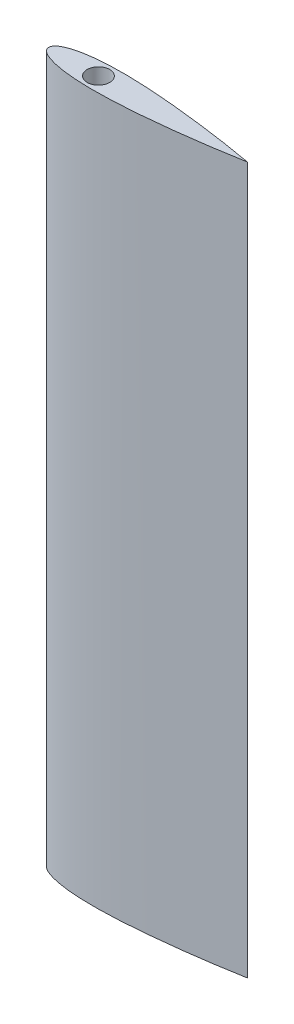
SolidWorks part; units mm, degrees
material "Polyurethane Foam Rigid"
ref_plane "Front Plane" through (0, 0, 0) normal (0, 0, 1) x (1, 0, 0)
ref_plane "Top Plane" through (0, 0, 0) normal (0, 1, 0) x (1, 0, 0)
ref_plane "Right Plane" through (0, 0, 0) normal (1, 0, 0) x (0, 0, -1)
ref_plane "Plane4" through (0, 31.75, 0) normal (0, 1, 0) x (1, 0, 0)
sketch "rootSketch" plane through (0, 31.75, 0) normal (0, 1, 0) x (1, 0, 0)
  line L0 (0, 0) -> (1500, 0) construction
  line L2 (13, -3.9) -> (13, 3.9) construction
  line L3 (0, 0) -> (52, 0) construction
  spline S0 degree 4 poles (0, 0) (0, 0.0566) (0.0054, 0.148) (0.0261, 0.2802) (0.0778, 0.4522) (0.1471, 0.6119) (0.2485, 0.786) (0.3924, 0.9775) (0.5992, 1.1954) (0.9058, 1.4518) (1.3705, 1.7579) (2.0783, 2.1191) (3.1757, 2.542) (4.8233, 2.9987) (7.2754, 3.453) (10.4387, 3.7805) (14.1293, 3.9293) (18.1436, 3.8963) (22.1517, 3.7223) (25.6562, 3.476) (28.6515, 3.2136) (31.6507, 2.914) (34.1342, 2.6396) (36.6395, 2.3366) (39.5995, 1.9537) (42.1279, 1.6007) (44.5332, 1.2475) (47.1211, 0.8374) (48.9103, 0.5455) (51.4233, 0.1075) (52.8542, -0.154) (54.9428, -0.5501) (55.9597, -0.7584) (56.7861, -0.9233) (56.9961, -0.9696) (57.2092, -1.0126) knots 0 0 0 0 0 0.003841 0.006235 0.009072 0.012193 0.015657 0.019917 0.025339 0.032593 0.042799 0.057705 0.079311 0.112503 0.158973 0.227236 0.2955 0.363764 0.432028 0.500292 0.534424 0.568556 0.63682 0.670952 0.705084 0.773347 0.807479 0.841611 0.875743 0.909875 0.954938 0.977469 0.988734 1 1 1 1 1 construction
  spline S1 degree 4 poles (0, 0) (0, 0.0566) (0.0054, 0.148) (0.0261, 0.2802) (0.0778, 0.4522) (0.1471, 0.6119) (0.2485, 0.786) (0.3924, 0.9775) (0.5992, 1.1954) (0.9058, 1.4518) (1.3705, 1.7579) (2.0783, 2.1191) (3.1757, 2.542) (4.8233, 2.9987) (7.2754, 3.453) (10.4387, 3.7805) (14.1293, 3.9293) (18.1436, 3.8963) (22.1517, 3.7223) (25.6562, 3.476) (28.6515, 3.2136) (31.6507, 2.914) (34.1342, 2.6396) (36.6395, 2.3366) (39.5995, 1.9537) (42.1279, 1.6007) (44.5332, 1.2475) (47.1211, 0.8374) (48.9103, 0.5455) (50.6553, 0.2414) (51.551, 0.0816) (52, 0) knots 0 0 0 0 0 0.003841 0.006235 0.009072 0.012193 0.015657 0.019917 0.025339 0.032593 0.042799 0.057705 0.079311 0.112503 0.158973 0.227236 0.2955 0.363764 0.432028 0.500292 0.534424 0.568556 0.63682 0.670952 0.705084 0.773347 0.807479 0.841611 0.875743 0.909875 0.909875 0.909875 0.909875 0.909875
  spline S2 degree 4 poles (0, 0) (0, -0.0566) (0.0054, -0.148) (0.0261, -0.2802) (0.0778, -0.4522) (0.1471, -0.6119) (0.2485, -0.786) (0.3924, -0.9775) (0.5992, -1.1954) (0.9058, -1.4518) (1.3705, -1.7579) (2.0783, -2.1191) (3.1757, -2.542) (4.8233, -2.9987) (7.2754, -3.453) (10.4387, -3.7805) (14.1293, -3.9293) (18.1436, -3.8963) (22.1517, -3.7223) (25.6562, -3.476) (28.6515, -3.2136) (31.6507, -2.914) (34.1342, -2.6396) (36.6395, -2.3366) (39.5995, -1.9537) (42.1279, -1.6007) (44.5332, -1.2475) (47.1211, -0.8374) (48.9103, -0.5455) (51.4233, -0.1075) (52.8542, 0.154) (54.9428, 0.5501) (55.9597, 0.7584) (56.7861, 0.9233) (56.9961, 0.9696) (57.2092, 1.0126) knots 0 0 0 0 0 0.003841 0.006235 0.009072 0.012193 0.015657 0.019917 0.025339 0.032593 0.042799 0.057705 0.079311 0.112503 0.158973 0.227236 0.2955 0.363764 0.432028 0.500292 0.534424 0.568556 0.63682 0.670952 0.705084 0.773347 0.807479 0.841611 0.875743 0.909875 0.954938 0.977469 0.988734 1 1 1 1 1 construction
  spline S3 degree 4 poles (0, 0) (0, -0.0566) (0.0054, -0.148) (0.0261, -0.2802) (0.0778, -0.4522) (0.1471, -0.6119) (0.2485, -0.786) (0.3924, -0.9775) (0.5992, -1.1954) (0.9058, -1.4518) (1.3705, -1.7579) (2.0783, -2.1191) (3.1757, -2.542) (4.8233, -2.9987) (7.2754, -3.453) (10.4387, -3.7805) (14.1293, -3.9293) (18.1436, -3.8963) (22.1517, -3.7223) (25.6562, -3.476) (28.6515, -3.2136) (31.6507, -2.914) (34.1342, -2.6396) (36.6395, -2.3366) (39.5995, -1.9537) (42.1279, -1.6007) (44.5332, -1.2475) (47.1211, -0.8374) (48.9103, -0.5455) (50.6553, -0.2414) (51.551, -0.0816) (52, 0) knots 0 0 0 0 0 0.003841 0.006235 0.009072 0.012193 0.015657 0.019917 0.025339 0.032593 0.042799 0.057705 0.079311 0.112503 0.158973 0.227236 0.2955 0.363764 0.432028 0.500292 0.534424 0.568556 0.63682 0.670952 0.705084 0.773347 0.807479 0.841611 0.875743 0.909875 0.909875 0.909875 0.909875 0.909875
  point P10 (13, 0)
  dimension "incidenceAngle" = 0
  dimension "rootChord" = 52
  dimension "rootQuarterChord" = 13
  dimension "rootMaxThickness" = 7.8
ref_plane "Plane1" through (0, 216.6684, 0) normal (0, 1, 0) x (1, 0, 0)
sketch "tipSketch" plane through (0, 216.6684, 0) normal (0, 1, 0) x (1, 0, 0)
  line L0 (216.8234, 0) -> (518.1352, 0) construction
  line L3 (0, 0) -> (52, 0) construction
  line L4 (13, -3.9) -> (13, 3.9) construction
  spline S0 degree 4 poles (0, 0) (0, 0.0566) (0.0054, 0.148) (0.0261, 0.2802) (0.0778, 0.4522) (0.1471, 0.6119) (0.2485, 0.786) (0.3924, 0.9775) (0.5992, 1.1954) (0.9058, 1.4518) (1.3705, 1.7579) (2.0783, 2.1191) (3.1757, 2.542) (4.8233, 2.9987) (7.2754, 3.453) (10.4387, 3.7805) (14.1293, 3.9293) (18.1436, 3.8963) (22.1517, 3.7223) (25.6562, 3.476) (28.6515, 3.2136) (31.6507, 2.914) (34.1342, 2.6396) (36.6395, 2.3366) (39.5995, 1.9537) (42.1279, 1.6007) (44.5332, 1.2475) (47.1211, 0.8374) (48.9103, 0.5455) (51.4233, 0.1075) (52.8542, -0.154) (54.9428, -0.5501) (55.9597, -0.7584) (56.7861, -0.9233) (56.9961, -0.9696) (57.2092, -1.0126) knots 0 0 0 0 0 0.003841 0.006235 0.009072 0.012193 0.015657 0.019917 0.025339 0.032593 0.042799 0.057705 0.079311 0.112503 0.158973 0.227236 0.2955 0.363764 0.432028 0.500292 0.534424 0.568556 0.63682 0.670952 0.705084 0.773347 0.807479 0.841611 0.875743 0.909875 0.954938 0.977469 0.988734 1 1 1 1 1 construction
  spline S1 degree 4 poles (0, 0) (0, 0.0566) (0.0054, 0.148) (0.0261, 0.2802) (0.0778, 0.4522) (0.1471, 0.6119) (0.2485, 0.786) (0.3924, 0.9775) (0.5992, 1.1954) (0.9058, 1.4518) (1.3705, 1.7579) (2.0783, 2.1191) (3.1757, 2.542) (4.8233, 2.9987) (7.2754, 3.453) (10.4387, 3.7805) (14.1293, 3.9293) (18.1436, 3.8963) (22.1517, 3.7223) (25.6562, 3.476) (28.6515, 3.2136) (31.6507, 2.914) (34.1342, 2.6396) (36.6395, 2.3366) (39.5995, 1.9537) (42.1279, 1.6007) (44.5332, 1.2475) (47.1211, 0.8374) (48.9103, 0.5455) (50.6553, 0.2414) (51.551, 0.0816) (52, 0) knots 0 0 0 0 0 0.003841 0.006235 0.009072 0.012193 0.015657 0.019917 0.025339 0.032593 0.042799 0.057705 0.079311 0.112503 0.158973 0.227236 0.2955 0.363764 0.432028 0.500292 0.534424 0.568556 0.63682 0.670952 0.705084 0.773347 0.807479 0.841611 0.875743 0.909875 0.909875 0.909875 0.909875 0.909875
  spline S2 degree 4 poles (0, 0) (0, -0.0566) (0.0054, -0.148) (0.0261, -0.2802) (0.0778, -0.4522) (0.1471, -0.6119) (0.2485, -0.786) (0.3924, -0.9775) (0.5992, -1.1954) (0.9058, -1.4518) (1.3705, -1.7579) (2.0783, -2.1191) (3.1757, -2.542) (4.8233, -2.9987) (7.2754, -3.453) (10.4387, -3.7805) (14.1293, -3.9293) (18.1436, -3.8963) (22.1517, -3.7223) (25.6562, -3.476) (28.6515, -3.2136) (31.6507, -2.914) (34.1342, -2.6396) (36.6395, -2.3366) (39.5995, -1.9537) (42.1279, -1.6007) (44.5332, -1.2475) (47.1211, -0.8374) (48.9103, -0.5455) (51.4233, -0.1075) (52.8542, 0.154) (54.9428, 0.5501) (55.9597, 0.7584) (56.7861, 0.9233) (56.9961, 0.9696) (57.2092, 1.0126) knots 0 0 0 0 0 0.003841 0.006235 0.009072 0.012193 0.015657 0.019917 0.025339 0.032593 0.042799 0.057705 0.079311 0.112503 0.158973 0.227236 0.2955 0.363764 0.432028 0.500292 0.534424 0.568556 0.63682 0.670952 0.705084 0.773347 0.807479 0.841611 0.875743 0.909875 0.954938 0.977469 0.988734 1 1 1 1 1 construction
  spline S3 degree 4 poles (0, 0) (0, -0.0566) (0.0054, -0.148) (0.0261, -0.2802) (0.0778, -0.4522) (0.1471, -0.6119) (0.2485, -0.786) (0.3924, -0.9775) (0.5992, -1.1954) (0.9058, -1.4518) (1.3705, -1.7579) (2.0783, -2.1191) (3.1757, -2.542) (4.8233, -2.9987) (7.2754, -3.453) (10.4387, -3.7805) (14.1293, -3.9293) (18.1436, -3.8963) (22.1517, -3.7223) (25.6562, -3.476) (28.6515, -3.2136) (31.6507, -2.914) (34.1342, -2.6396) (36.6395, -2.3366) (39.5995, -1.9537) (42.1279, -1.6007) (44.5332, -1.2475) (47.1211, -0.8374) (48.9103, -0.5455) (50.6553, -0.2414) (51.551, -0.0816) (52, 0) knots 0 0 0 0 0 0.003841 0.006235 0.009072 0.012193 0.015657 0.019917 0.025339 0.032593 0.042799 0.057705 0.079311 0.112503 0.158973 0.227236 0.2955 0.363764 0.432028 0.500292 0.534424 0.568556 0.63682 0.670952 0.705084 0.773347 0.807479 0.841611 0.875743 0.909875 0.909875 0.909875 0.909875 0.909875
  point P10 (13, 0)
  dimension "incidenceAngle" = 0
  dimension "tipChord" = 52
  dimension "tipQuarterChord" = 13
  dimension "tipMaxThickness" = 7.8
  dimension "sweepOffset" = 0
loft "Loft1" add profiles "rootSketch", "tipSketch" connector at (52, 31.75, 0) connector at (52, 216.6684, 0)
ref_plane "Plane2" through (52, 0, 0) normal (1, 0, 0) x (0, 0, -1)
sketch "rudderSketch" plane through (0, 0, 0) normal (0, 0, 1) x (1, 0, 0)
  line L0 (52, 31.75) -> (52, 85.9171) construction
  line L1 (52, 31.75) -> (52, 194.2513) construction
  line L2 (52, 85.9171) -> (78, 85.9171) construction
  line L3 (52, 194.2513) -> (78, 194.2513) construction
  line L4 (78, 194.2513) -> (78, 85.9171)
  line L5 (78, 194.2513) -> (130, 194.2513)
  line L6 (78, 85.9171) -> (130, 85.9171)
  line L7 (130, 85.9171) -> (130, 194.2513)
  line L8 (129.5667, 86.3504) -> (129.5667, 193.818)
  line L9 (78.4333, 193.818) -> (129.5667, 193.818)
  line L10 (78.4333, 193.818) -> (78.4333, 86.3504)
  line L11 (78.4333, 86.3504) -> (129.5667, 86.3504)
  dimension "rudderStartyLoc" = 54.1671
  dimension "rudderEndyLoc" = 162.5013
  dimension "rudderStartxLoc" = 26
  dimension "rudderEndeLoc" = 26
  dimension "D1" = 52
  dimension "D2" = 52
extrude "Cut-Extrude1" [suppressed] cut sketch "rudderSketch" against normal blind 200 and the other way blind 200
sketch "Sketch1" plane through (0, 31.75, 0) normal (0, 1, 0) x (1, 0, 0)
  line L0 (0, 0) -> (52, 0) construction
  line L2 (52, 3.9004) -> (52, -3.9004) construction
  line L4 (0, -3.9004) -> (0, 3.9004) construction
  line L6 (13, 3.8615) -> (13, -3.8615) construction
  circle A0 centre (13, 0) radius 2.95
  circle A1 centre (13, 0) radius 1.9304 construction
  spline S0 degree 3 poles (52, 0) (49.8075, 0.3984) (45.4111, 1.1322) (39.8961, 1.9224) (35.4744, 2.4815) (32.1534, 2.8618) (28.8277, 3.1988) (25.4973, 3.4855) (22.7181, 3.674) (20.4925, 3.7875) (18.8224, 3.8515) (17.1515, 3.8919) (15.4802, 3.9055) (13.8089, 3.8885) (12.1383, 3.836) (10.4694, 3.7424) (9.0816, 3.6237) (7.9743, 3.4989) (7.1459, 3.3887) (6.3202, 3.2597) (5.4981, 3.1092) (4.681, 2.9337) (3.8708, 2.7284) (3.0706, 2.4866) (2.2858, 2.1982) (1.6528, 1.9059) (1.1703, 1.6264) (0.8267, 1.3881) (0.5106, 1.1133) (0.2403, 0.7926) (0.0469, 0.4177) (0, 0.1393) (0, 0) knots 0 0 0 0 0.062499 0.124998 0.156248 0.187497 0.218747 0.249996 0.281246 0.296871 0.312496 0.32812 0.343745 0.35937 0.374995 0.39062 0.406244 0.414057 0.421869 0.429681 0.437494 0.445306 0.453119 0.460931 0.468743 0.476556 0.480462 0.484368 0.488274 0.492181 0.496087 0.499993 0.499993 0.499993 0.499993 construction
  spline S1 degree 3 poles (0, 0) (0, -0.1393) (0.0469, -0.4177) (0.2403, -0.7926) (0.5106, -1.1133) (0.8267, -1.3881) (1.1703, -1.6264) (1.6528, -1.9059) (2.2858, -2.1982) (3.0706, -2.4866) (3.8708, -2.7284) (4.681, -2.9337) (5.4981, -3.1092) (6.3202, -3.2597) (7.1459, -3.3887) (7.9743, -3.4989) (9.0816, -3.6237) (10.4694, -3.7424) (12.1383, -3.836) (13.8089, -3.8885) (15.4802, -3.9055) (17.1515, -3.8919) (18.8224, -3.8515) (20.4925, -3.7875) (22.7181, -3.674) (25.4973, -3.4855) (28.8277, -3.1988) (32.1534, -2.8618) (35.4744, -2.4815) (39.8961, -1.9224) (45.4111, -1.1322) (49.8075, -0.3984) (52, 0) knots 0.499993 0.499993 0.499993 0.499993 0.503899 0.507806 0.511712 0.515618 0.519525 0.523431 0.531243 0.539056 0.546869 0.554681 0.562494 0.570306 0.578119 0.585932 0.593744 0.60937 0.624995 0.64062 0.656245 0.67187 0.687496 0.703121 0.718746 0.749996 0.781247 0.812497 0.843748 0.874998 0.937499 1 1 1 1 construction
  dimension "D1" = 5.9
  dimension "D2" = 3.8608
  dimension "D3" = 52
  dimension "D4" = 13
extrude "Cut-Extrude2" cut sketch "Sketch1<2>" along normal through all
sketch "Sketch1<2>" plane through (0, 31.75, 0) normal (0, 1, 0) x (1, 0, 0) same geometry as "Sketch1"
extrude "Boss-Extrude1" [suppressed] add sketch "Sketch1" along normal up to surface and the other way blind 17.145 separate body up to face at (13, 216.6684, -2.95)
sketch "Sketch3" plane through (0, 31.75, 0) normal (0, 1, 0) x (1, 0, 0)
  circle A0 centre (13, 0) radius 3.9688
  circle A1 centre (13, 0) radius 2.95 construction
  dimension "D1" = 7.9375
extrude "Boss-Extrude2" [suppressed] add sketch "Sketch3" against normal blind 3.81
ref_axis "Axis1" [suppressed] through (15.5748, 28.575, 0) along (0, -1, 0)
ref_plane "Plane3" [suppressed] through (15.5748, 0, 0) normal (-1, 0, 0) x (0, -1, 0)
sketch "Sketch2" [suppressed] plane through (15.5748, 0, 0) normal (1, 0, 0) x (0, 0, -1)
  line L0 (0, 14.605) -> (0, 27.94) construction
  line L1 (6.35, 23.9712) -> (3.175, 23.9712)
  line L2 (6.35, 23.9712) -> (6.35, 27.94)
  line L3 (6.35, 27.94) -> (3.175, 27.94)
  line L4 (19.05, 23.9713) -> (19.05, 27.94) construction
  line L5 (-3.175, 14.605) -> (3.175, 14.605) construction
  line L7 (-3.175, 27.94) -> (3.175, 27.94) construction
  line L8 (3.175, 15.24) -> (3.175, 19.2087)
  line L9 (6.35, 15.24) -> (3.175, 15.24)
  line L10 (6.35, 15.24) -> (6.35, 19.2087)
  line L11 (6.35, 19.2087) -> (3.175, 19.2087)
  line L12 (19.05, 15.24) -> (19.05, 19.2088) construction
  line L13 (3.175, 23.9712) -> (3.175, 27.94)
  line L14 (-3.175, 15.24) -> (-3.175, 19.2087) construction
  line L15 (-3.175, 23.9712) -> (-3.175, 27.94) construction
  line L16 (3.175, 14.605) -> (3.175, 27.94) construction
  line L17 (-3.175, 15.24) -> (19.05, 15.24) construction
  line L18 (-3.175, 19.2087) -> (19.05, 19.2088) construction
  line L19 (-3.175, 23.9712) -> (19.05, 23.9713) construction
  line L20 (-3.175, 27.94) -> (19.05, 27.94) construction
  line L21 (-3.9688, 27.94) -> (3.9687, 27.94) construction
  dimension "D1" = 3.9688
  dimension "D2" = 12.7
  dimension "D3" = 12.7
  dimension "D4" = 6.35
revolve "Revolve1" [suppressed] add sketch "Sketch2" angle 360 about L0
sketch "Sketch4" [suppressed] plane through (0, 14.605, 0) normal (0, -1, 0) x (-1, 0, 0)
  circle A0 centre (-15.5748, 0) radius 3.0226
  circle A1 centre (-15.5748, 0) radius 3.175 construction
  dimension "D1" = 6.0452
extrude "Cut-Extrude3" [suppressed] cut sketch "Sketch4" along normal blind 0.381 from offset 1.27 flip side to cut offset against normal yes
sketch "Sketch5" [suppressed] plane through (0, 27.94, 0) normal (0, -1, 0) x (1, 0, 0)
  line L1 (13.1936, 3.175) -> (17.9561, 3.175)
  line L3 (13.1936, -3.175) -> (17.9561, -3.175)
  arc A0 (17.9561, 3.175) -> (13.1936, 3.175) centre (15.5748, 0) ccw
  circle A1 centre (15.5748, 0) radius 3.9688 construction
  circle A2 centre (15.5748, 0) radius 3.175 construction
  arc A3 (13.1936, -3.175) -> (17.9561, -3.175) centre (15.5748, 0) ccw
extrude "Cut-Extrude6" [suppressed] cut sketch "Sketch5" against normal up to surface (3.81 mm away) up to face at (13, 31.75, 2.95)
sketch "Sketch6" plane through (0, 0, 0) normal (0, 0, 1) x (1, 0, 0)
  line L0 (52, 31.75) -> (52, 216.6684) construction
  line L1 (52, 216.6684) -> (0, 216.6684)
  line L2 (52, 216.6684) -> (52, 31.75)
  line L3 (52, 31.75) -> (0, 31.75)
  line L4 (0, 216.6684) -> (0, 31.75)
  line L5 (0, 31.75) -> (0, 216.6684) construction
  line L6 (52, 216.6684) -> (0, 216.6684) construction
  line L9 (0, 31.75) -> (52, 31.75) construction
equation "\"rootChord@rootSketch\"=(\"rootChord\"+\"rootChord\")/2"
equation "\"incidenceAngle@rootSketch\"=(\"incidentAngle\"+\"incidentAngle\")/2"
equation "\"rootQuarterChord@rootSketch\" = \"rootChord@rootSketch\" / 4"
equation "\"rootMaxThickness@rootSketch\" = \"rootChord\" * \"NACAairfoil\" / 100"
equation "\"halfSpan@Plane1\"= \"rootChord@rootSketch\" * ( 1 + \"taperRatio\" ) / 2 * \"aspectRatio\""
equation "\"incidenceAngle@tipSketch\" = \"incidenceAngle@rootSketch\""
equation "\"tipChord@tipSketch\"= \"rootChord@rootSketch\" * \"taperRatio\""
equation "\"tipQuarterChord@tipSketch\"=\"tipChord@tipSketch\"/4"
equation "\"tipMaxThickness@tipSketch\"=\"tipChord@tipSketch\"*\"NACAairfoil\"/100"
equation "\"rootChord@Plane2\"=\"rootChord@rootSketch\""
equation "\"rudderCenter\"= 0.5'Center of the rudder as a percentage of half span"
equation "\"rudderWidth\"= 0.5'Width of the rudder as a percentage of half span"
equation "\"rudderStartyLoc@rudderSketch\"=\"halfSpan@Plane1\" *  ( \"rudderCenter\" - \"rudderWidth\" / 2 )"
equation "\"rudderEndyLoc@rudderSketch\"=\"halfSpan@Plane1\" *  ( \"rudderCenter\" + \"rudderWidth\" / 2 )"
equation "\"rudderStartxLoc@rudderSketch\"=\"rudderStartyLoc@rudderSketch\"*tan ( \"sweepAngle\" ) + 0.5*(\"rootChord@rootSketch\" + \"rudderStartyLoc@rudderSketch\"*(((\"tipChord@tipSketch\"-\"rootChord@rootSketch\")/\"halfSpan@Plane1\")))"
equation "\"rudderEndeLoc@rudderSketch\"=\"rudderStartyLoc@rudderSketch\"*tan ( \"sweepAngle\" ) + 0.5*(\"rootChord@rootSketch\" + \"rudderStartyLoc@rudderSketch\"*(((\"tipChord@tipSketch\"-\"rootChord@rootSketch\")/\"halfSpan@Plane1\")))"
equation "\"D1@rudderSketch\"=1*\"rootChord@rootSketch\""
equation "\"D2@rudderSketch\"=1*\"rootChord@rootSketch\""
equation "\"D3@rudderSketch\"=\"halfSpan@Plane1\"/500"
equation "\"sweepOffset@tipSketch\" = \"halfSpan@Plane1\" * tan ( \"sweepAngle\" ) "
equation "\"D2@tipSketch\"=\"tipChord@tipSketch\"*tan(\"incidentAngle\")"
equation "\"rootChord\"= 0.052"
equation "\"NACAairfoil\"= 0015"
equation "\"incidentAngle\"= 0"
equation "\"aspectRatio\"= 4.1667"
equation "\"taperRatio\"= 1"
equation "\"sweepAngle\"= 0"
equation "\"D4@Sketch1\"=0.25*\"D3@Sketch1\""
